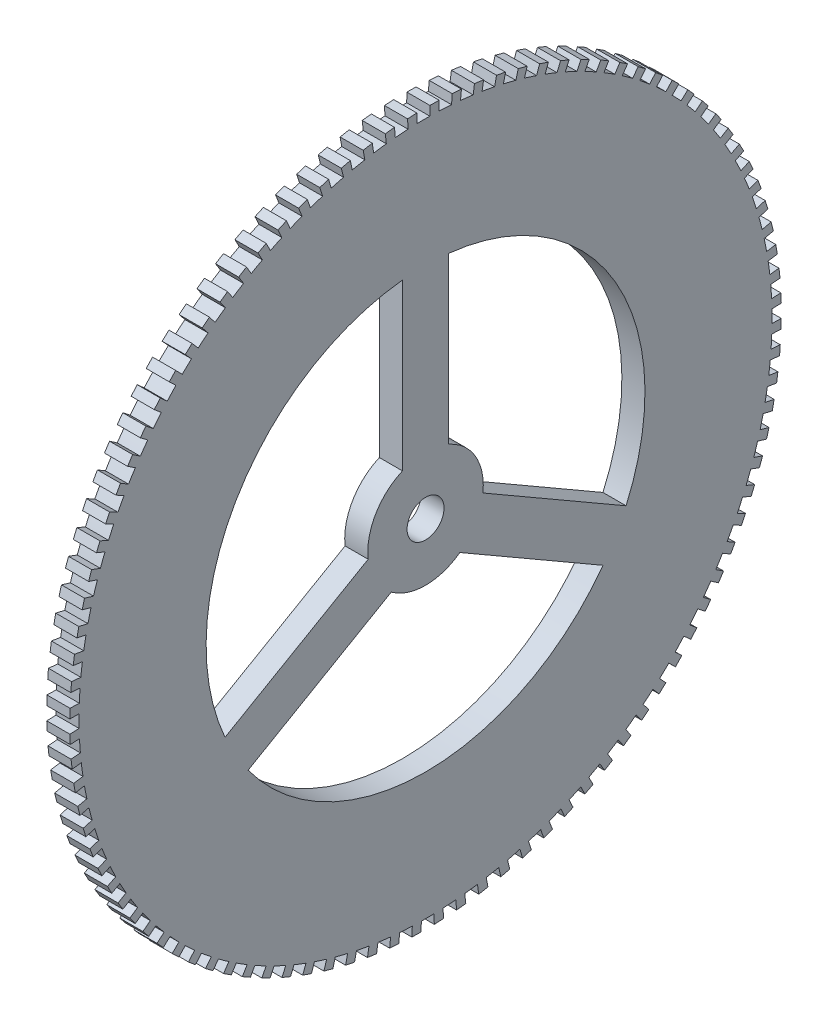
SolidWorks part; units mm, degrees
ref_plane "Front Plane" through (0, 0, 0) normal (0, 0, 1) x (1, 0, 0)
ref_plane "Top Plane" through (0, 0, 0) normal (0, 1, 0) x (1, 0, 0)
ref_plane "Right Plane" through (0, 0, 0) normal (1, 0, 0) x (0, 0, -1)
sketch "Sketch1" plane through (0, 0, 0) normal (1, 0, 0) x (0, 0, -1)
  line L0 (5, 47.2361) -> (5, 11.4564)
  line L1 (-26.7494, 70.0676) -> (-27.4627, 71.9361)
  line L2 (-5, 47.2361) -> (-5, 11.4564)
  line L3 (0, 55) -> (0, -55) construction
  line L4 (43.4077, -19.2879) -> (12.4216, -1.3981)
  line L5 (38.4077, -27.9482) -> (7.4216, -10.0583)
  line L6 (-38.4077, -27.9482) -> (-7.4216, -10.0583)
  line L7 (-43.4077, -19.2879) -> (-12.4216, -1.3981)
  line L8 (-24.9211, 70.7385) -> (-25.5942, 72.6494)
  line L9 (-25.5942, 72.6494) -> (-27.4627, 71.9361)
  line L10 (-22.297, 71.609) -> (-22.8916, 73.5185)
  line L11 (-20.982, 74.1131) -> (-22.8916, 73.5185)
  line L12 (-20.4302, 72.1638) -> (-20.982, 74.1131)
  line L13 (-17.7567, 72.8677) -> (-18.2302, 74.8108)
  line L14 (-16.287, 75.2843) -> (-18.2302, 74.8108)
  line L15 (-15.8587, 73.3042) -> (-16.287, 75.2843)
  line L16 (-13.1462, 73.8389) -> (-13.4968, 75.8079)
  line L17 (-11.5278, 76.1585) -> (-13.4968, 75.8079)
  line L18 (-11.2246, 74.1553) -> (-11.5278, 76.1585)
  line L19 (-8.4839, 74.5186) -> (-8.7102, 76.5058)
  line L20 (-6.723, 76.732) -> (-8.7102, 76.5058)
  line L21 (-6.5462, 74.7138) -> (-6.723, 76.732)
  line L22 (-3.7881, 74.9043) -> (-3.8891, 76.9017)
  line L23 (-1.8917, 77.0027) -> (-3.8891, 76.9017)
  line L24 (-1.8419, 74.9774) -> (-1.8917, 77.0027)
  line L25 (0.9226, 74.9943) -> (0.9472, 76.9942)
  line L26 (2.9471, 76.9696) -> (0.9472, 76.9942)
  line L27 (2.8696, 74.9451) -> (2.9471, 76.9696)
  line L28 (5.6298, 74.7884) -> (5.7799, 76.7828)
  line L29 (7.7742, 76.6326) -> (5.7799, 76.7828)
  line L30 (7.5698, 74.617) -> (7.7742, 76.6326)
  line L31 (10.3146, 74.2873) -> (10.5897, 76.2683)
  line L32 (12.5707, 75.9933) -> (10.5897, 76.2683)
  line L33 (12.2401, 73.9945) -> (12.5707, 75.9933)
  line L34 (14.9588, 73.4931) -> (15.3577, 75.4529)
  line L35 (17.3176, 75.054) -> (15.3577, 75.4529)
  line L36 (16.8621, 73.0799) -> (17.3176, 75.054)
  line L37 (19.544, 72.4088) -> (20.0652, 74.3397)
  line L38 (21.9961, 73.8185) -> (20.0652, 74.3397)
  line L39 (21.4175, 71.8769) -> (21.9961, 73.8185)
  line L40 (24.052, 71.0387) -> (24.6934, 72.9331)
  line L41 (26.5878, 72.2917) -> (24.6934, 72.9331)
  line L42 (25.8884, 70.3903) -> (26.5878, 72.2917)
  line L43 (28.4651, 69.3883) -> (29.2242, 71.2387)
  line L44 (31.0745, 70.4796) -> (29.2242, 71.2387)
  line L45 (30.2572, 68.6258) -> (31.0745, 70.4796)
  line L46 (32.7659, 67.4641) -> (33.6396, 69.2631)
  line L47 (35.4387, 68.3893) -> (33.6396, 69.2631)
  line L48 (34.5065, 66.5905) -> (35.4387, 68.3893)
  line L49 (36.9373, 65.2735) -> (37.9223, 67.0142)
  line L50 (39.6629, 66.0292) -> (37.9223, 67.0142)
  line L51 (38.6197, 64.2924) -> (39.6629, 66.0292)
  line L52 (40.963, 62.8254) -> (42.0553, 64.5008)
  line L53 (43.7307, 63.4084) -> (42.0553, 64.5008)
  line L54 (42.5805, 61.7406) -> (43.7307, 63.4084)
  line L55 (44.827, 60.1294) -> (46.0224, 61.7328)
  line L56 (47.6258, 60.5374) -> (46.0224, 61.7328)
  line L57 (46.3732, 58.9451) -> (47.6258, 60.5374)
  line L58 (48.5141, 57.196) -> (49.8078, 58.7212)
  line L59 (51.333, 57.4275) -> (49.8078, 58.7212)
  line L60 (49.9828, 55.917) -> (51.333, 57.4275)
  line L61 (52.0097, 54.0369) -> (53.3967, 55.4779)
  line L62 (54.8376, 54.091) -> (53.3967, 55.4779)
  line L63 (53.3953, 52.6683) -> (54.8376, 54.091)
  line L64 (55.3001, 50.6646) -> (56.7748, 52.0156)
  line L65 (58.1258, 50.541) -> (56.7748, 52.0156)
  line L66 (56.597, 49.2116) -> (58.1258, 50.541)
  line L67 (58.3722, 47.0923) -> (59.9288, 48.3481)
  line L68 (61.1846, 46.7915) -> (59.9288, 48.3481)
  line L69 (59.5753, 45.5607) -> (61.1846, 46.7915)
  line L70 (61.214, 43.3341) -> (62.8464, 44.4897)
  line L71 (64.0019, 42.8573) -> (62.8464, 44.4897)
  line L72 (62.3185, 41.7301) -> (64.0019, 42.8573)
  line L73 (63.8142, 39.405) -> (65.5159, 40.4558)
  line L74 (66.5667, 38.754) -> (65.5159, 40.4558)
  line L75 (64.8158, 37.7347) -> (66.5667, 38.754)
  line L76 (66.1625, 35.3203) -> (67.9268, 36.2621)
  line L77 (68.8687, 34.4978) -> (67.9268, 36.2621)
  line L78 (67.0573, 33.5904) -> (68.8687, 34.4978)
  line L79 (68.2497, 31.0962) -> (70.0697, 31.9254)
  line L80 (70.899, 30.1054) -> (70.0697, 31.9254)
  line L81 (69.0341, 29.3136) -> (70.899, 30.1054)
  line L82 (70.0676, 26.7494) -> (71.9361, 27.4627)
  line L83 (72.6494, 25.5942) -> (71.9361, 27.4627)
  line L84 (70.7385, 24.9211) -> (72.6494, 25.5942)
  line L85 (71.609, 22.297) -> (73.5185, 22.8916)
  line L86 (74.1131, 20.982) -> (73.5185, 22.8916)
  line L87 (72.1638, 20.4302) -> (74.1131, 20.982)
  line L88 (72.8677, 17.7567) -> (74.8108, 18.2302)
  line L89 (75.2843, 16.287) -> (74.8108, 18.2302)
  line L90 (73.3042, 15.8587) -> (75.2843, 16.287)
  line L91 (73.8389, 13.1462) -> (75.8079, 13.4968)
  line L92 (76.1585, 11.5278) -> (75.8079, 13.4968)
  line L93 (74.1553, 11.2246) -> (76.1585, 11.5278)
  line L94 (74.5186, 8.4839) -> (76.5058, 8.7102)
  line L95 (76.732, 6.723) -> (76.5058, 8.7102)
  line L96 (74.7138, 6.5462) -> (76.732, 6.723)
  line L97 (74.9043, 3.7881) -> (76.9017, 3.8891)
  line L98 (77.0027, 1.8917) -> (76.9017, 3.8891)
  line L99 (74.9774, 1.8419) -> (77.0027, 1.8917)
  line L100 (74.9943, -0.9226) -> (76.9942, -0.9472)
  line L101 (76.9696, -2.9471) -> (76.9942, -0.9472)
  line L102 (74.9451, -2.8696) -> (76.9696, -2.9471)
  line L103 (74.7884, -5.6298) -> (76.7828, -5.7799)
  line L104 (76.6326, -7.7742) -> (76.7828, -5.7799)
  line L105 (74.617, -7.5698) -> (76.6326, -7.7742)
  line L106 (74.2873, -10.3146) -> (76.2683, -10.5897)
  line L107 (75.9933, -12.5707) -> (76.2683, -10.5897)
  line L108 (73.9945, -12.2401) -> (75.9933, -12.5707)
  line L109 (73.4931, -14.9588) -> (75.4529, -15.3577)
  line L110 (75.054, -17.3176) -> (75.4529, -15.3577)
  line L111 (73.0799, -16.8621) -> (75.054, -17.3176)
  line L112 (72.4088, -19.544) -> (74.3397, -20.0652)
  line L113 (73.8185, -21.9961) -> (74.3397, -20.0652)
  line L114 (71.8769, -21.4175) -> (73.8185, -21.9961)
  line L115 (71.0387, -24.052) -> (72.9331, -24.6934)
  line L116 (72.2917, -26.5878) -> (72.9331, -24.6934)
  line L117 (70.3903, -25.8884) -> (72.2917, -26.5878)
  line L118 (69.3883, -28.4651) -> (71.2387, -29.2242)
  line L119 (70.4796, -31.0745) -> (71.2387, -29.2242)
  line L120 (68.6258, -30.2572) -> (70.4796, -31.0745)
  line L121 (67.4641, -32.7659) -> (69.2631, -33.6396)
  line L122 (68.3893, -35.4387) -> (69.2631, -33.6396)
  line L123 (66.5905, -34.5065) -> (68.3893, -35.4387)
  line L124 (65.2735, -36.9373) -> (67.0142, -37.9223)
  line L125 (66.0292, -39.6629) -> (67.0142, -37.9223)
  line L126 (64.2924, -38.6197) -> (66.0292, -39.6629)
  line L127 (62.8254, -40.963) -> (64.5008, -42.0553)
  line L128 (63.4084, -43.7307) -> (64.5008, -42.0553)
  line L129 (61.7406, -42.5805) -> (63.4084, -43.7307)
  line L130 (60.1294, -44.827) -> (61.7328, -46.0224)
  line L131 (60.5374, -47.6258) -> (61.7328, -46.0224)
  line L132 (58.9451, -46.3732) -> (60.5374, -47.6258)
  line L133 (57.196, -48.5141) -> (58.7212, -49.8078)
  line L134 (57.4275, -51.333) -> (58.7212, -49.8078)
  line L135 (55.917, -49.9828) -> (57.4275, -51.333)
  line L136 (54.0369, -52.0097) -> (55.4779, -53.3967)
  line L137 (54.091, -54.8376) -> (55.4779, -53.3967)
  line L138 (52.6683, -53.3953) -> (54.091, -54.8376)
  line L139 (50.6646, -55.3001) -> (52.0156, -56.7748)
  line L140 (50.541, -58.1258) -> (52.0156, -56.7748)
  line L141 (49.2116, -56.597) -> (50.541, -58.1258)
  line L142 (47.0923, -58.3722) -> (48.3481, -59.9288)
  line L143 (46.7915, -61.1846) -> (48.3481, -59.9288)
  line L144 (45.5607, -59.5753) -> (46.7915, -61.1846)
  line L145 (43.3341, -61.214) -> (44.4897, -62.8464)
  line L146 (42.8573, -64.0019) -> (44.4897, -62.8464)
  line L147 (41.7301, -62.3185) -> (42.8573, -64.0019)
  line L148 (39.405, -63.8142) -> (40.4558, -65.5159)
  line L149 (38.754, -66.5667) -> (40.4558, -65.5159)
  line L150 (37.7347, -64.8158) -> (38.754, -66.5667)
  line L151 (35.3203, -66.1625) -> (36.2621, -67.9268)
  line L152 (34.4978, -68.8687) -> (36.2621, -67.9268)
  line L153 (33.5904, -67.0573) -> (34.4978, -68.8687)
  line L154 (31.0962, -68.2497) -> (31.9254, -70.0697)
  line L155 (30.1054, -70.899) -> (31.9254, -70.0697)
  line L156 (29.3136, -69.0341) -> (30.1054, -70.899)
  line L157 (26.7494, -70.0676) -> (27.4627, -71.9361)
  line L158 (25.5942, -72.6494) -> (27.4627, -71.9361)
  line L159 (24.9211, -70.7385) -> (25.5942, -72.6494)
  line L160 (22.297, -71.609) -> (22.8916, -73.5185)
  line L161 (20.982, -74.1131) -> (22.8916, -73.5185)
  line L162 (20.4302, -72.1638) -> (20.982, -74.1131)
  line L163 (17.7567, -72.8677) -> (18.2302, -74.8108)
  line L164 (16.287, -75.2843) -> (18.2302, -74.8108)
  line L165 (15.8587, -73.3042) -> (16.287, -75.2843)
  line L166 (13.1462, -73.8389) -> (13.4968, -75.8079)
  line L167 (11.5278, -76.1585) -> (13.4968, -75.8079)
  line L168 (11.2246, -74.1553) -> (11.5278, -76.1585)
  line L169 (8.4839, -74.5186) -> (8.7102, -76.5058)
  line L170 (6.723, -76.732) -> (8.7102, -76.5058)
  line L171 (6.5462, -74.7138) -> (6.723, -76.732)
  line L172 (3.7881, -74.9043) -> (3.8891, -76.9017)
  line L173 (1.8917, -77.0027) -> (3.8891, -76.9017)
  line L174 (1.8419, -74.9774) -> (1.8917, -77.0027)
  line L175 (-0.9226, -74.9943) -> (-0.9472, -76.9942)
  line L176 (-2.9471, -76.9696) -> (-0.9472, -76.9942)
  line L177 (-2.8696, -74.9451) -> (-2.9471, -76.9696)
  line L178 (-5.6298, -74.7884) -> (-5.7799, -76.7828)
  line L179 (-7.7742, -76.6326) -> (-5.7799, -76.7828)
  line L180 (-7.5698, -74.617) -> (-7.7742, -76.6326)
  line L181 (-10.3146, -74.2873) -> (-10.5897, -76.2683)
  line L182 (-12.5707, -75.9933) -> (-10.5897, -76.2683)
  line L183 (-12.2401, -73.9945) -> (-12.5707, -75.9933)
  line L184 (-14.9588, -73.4931) -> (-15.3577, -75.4529)
  line L185 (-17.3176, -75.054) -> (-15.3577, -75.4529)
  line L186 (-16.8621, -73.0799) -> (-17.3176, -75.054)
  line L187 (-19.544, -72.4088) -> (-20.0652, -74.3397)
  line L188 (-21.9961, -73.8185) -> (-20.0652, -74.3397)
  line L189 (-21.4175, -71.8769) -> (-21.9961, -73.8185)
  line L190 (-24.052, -71.0387) -> (-24.6934, -72.9331)
  line L191 (-26.5878, -72.2917) -> (-24.6934, -72.9331)
  line L192 (-25.8884, -70.3903) -> (-26.5878, -72.2917)
  line L193 (-28.4651, -69.3883) -> (-29.2242, -71.2387)
  line L194 (-31.0745, -70.4796) -> (-29.2242, -71.2387)
  line L195 (-30.2572, -68.6258) -> (-31.0745, -70.4796)
  line L196 (-32.7659, -67.4641) -> (-33.6396, -69.2631)
  line L197 (-35.4387, -68.3893) -> (-33.6396, -69.2631)
  line L198 (-34.5065, -66.5905) -> (-35.4387, -68.3893)
  line L199 (-36.9373, -65.2735) -> (-37.9223, -67.0142)
  line L200 (-39.6629, -66.0292) -> (-37.9223, -67.0142)
  line L201 (-38.6197, -64.2924) -> (-39.6629, -66.0292)
  line L202 (-40.963, -62.8254) -> (-42.0553, -64.5008)
  line L203 (-43.7307, -63.4084) -> (-42.0553, -64.5008)
  line L204 (-42.5805, -61.7406) -> (-43.7307, -63.4084)
  line L205 (-44.827, -60.1294) -> (-46.0224, -61.7328)
  line L206 (-47.6258, -60.5374) -> (-46.0224, -61.7328)
  line L207 (-46.3732, -58.9451) -> (-47.6258, -60.5374)
  line L208 (-48.5141, -57.196) -> (-49.8078, -58.7212)
  line L209 (-51.333, -57.4275) -> (-49.8078, -58.7212)
  line L210 (-49.9828, -55.917) -> (-51.333, -57.4275)
  line L211 (-52.0097, -54.0369) -> (-53.3967, -55.4779)
  line L212 (-54.8376, -54.091) -> (-53.3967, -55.4779)
  line L213 (-53.3953, -52.6683) -> (-54.8376, -54.091)
  line L214 (-55.3001, -50.6646) -> (-56.7748, -52.0156)
  line L215 (-58.1258, -50.541) -> (-56.7748, -52.0156)
  line L216 (-56.597, -49.2116) -> (-58.1258, -50.541)
  line L217 (-58.3722, -47.0923) -> (-59.9288, -48.3481)
  line L218 (-61.1846, -46.7915) -> (-59.9288, -48.3481)
  line L219 (-59.5753, -45.5607) -> (-61.1846, -46.7915)
  line L220 (-61.214, -43.3341) -> (-62.8464, -44.4897)
  line L221 (-64.0019, -42.8573) -> (-62.8464, -44.4897)
  line L222 (-62.3185, -41.7301) -> (-64.0019, -42.8573)
  line L223 (-63.8142, -39.405) -> (-65.5159, -40.4558)
  line L224 (-66.5667, -38.754) -> (-65.5159, -40.4558)
  line L225 (-64.8158, -37.7347) -> (-66.5667, -38.754)
  line L226 (-66.1625, -35.3203) -> (-67.9268, -36.2621)
  line L227 (-68.8687, -34.4978) -> (-67.9268, -36.2621)
  line L228 (-67.0573, -33.5904) -> (-68.8687, -34.4978)
  line L229 (-68.2497, -31.0962) -> (-70.0697, -31.9254)
  line L230 (-70.899, -30.1054) -> (-70.0697, -31.9254)
  line L231 (-69.0341, -29.3136) -> (-70.899, -30.1054)
  line L232 (-70.0676, -26.7494) -> (-71.9361, -27.4627)
  line L233 (-72.6494, -25.5942) -> (-71.9361, -27.4627)
  line L234 (-70.7385, -24.9211) -> (-72.6494, -25.5942)
  line L235 (-71.609, -22.297) -> (-73.5185, -22.8916)
  line L236 (-74.1131, -20.982) -> (-73.5185, -22.8916)
  line L237 (-72.1638, -20.4302) -> (-74.1131, -20.982)
  line L238 (-72.8677, -17.7567) -> (-74.8108, -18.2302)
  line L239 (-75.2843, -16.287) -> (-74.8108, -18.2302)
  line L240 (-73.3042, -15.8587) -> (-75.2843, -16.287)
  line L241 (-73.8389, -13.1462) -> (-75.8079, -13.4968)
  line L242 (-76.1585, -11.5278) -> (-75.8079, -13.4968)
  line L243 (-74.1553, -11.2246) -> (-76.1585, -11.5278)
  line L244 (-74.5186, -8.4839) -> (-76.5058, -8.7102)
  line L245 (-76.732, -6.723) -> (-76.5058, -8.7102)
  line L246 (-74.7138, -6.5462) -> (-76.732, -6.723)
  line L247 (-74.9043, -3.7881) -> (-76.9017, -3.8891)
  line L248 (-77.0027, -1.8917) -> (-76.9017, -3.8891)
  line L249 (-74.9774, -1.8419) -> (-77.0027, -1.8917)
  line L250 (-74.9943, 0.9226) -> (-76.9942, 0.9472)
  line L251 (-76.9696, 2.9471) -> (-76.9942, 0.9472)
  line L252 (-74.9451, 2.8696) -> (-76.9696, 2.9471)
  line L253 (-74.7884, 5.6298) -> (-76.7828, 5.7799)
  line L254 (-76.6326, 7.7742) -> (-76.7828, 5.7799)
  line L255 (-74.617, 7.5698) -> (-76.6326, 7.7742)
  line L256 (-74.2873, 10.3146) -> (-76.2683, 10.5897)
  line L257 (-75.9933, 12.5707) -> (-76.2683, 10.5897)
  line L258 (-73.9945, 12.2401) -> (-75.9933, 12.5707)
  line L259 (-73.4931, 14.9588) -> (-75.4529, 15.3577)
  line L260 (-75.054, 17.3176) -> (-75.4529, 15.3577)
  line L261 (-73.0799, 16.8621) -> (-75.054, 17.3176)
  line L262 (-72.4088, 19.544) -> (-74.3397, 20.0652)
  line L263 (-73.8185, 21.9961) -> (-74.3397, 20.0652)
  line L264 (-71.8769, 21.4175) -> (-73.8185, 21.9961)
  line L265 (-71.0387, 24.052) -> (-72.9331, 24.6934)
  line L266 (-72.2917, 26.5878) -> (-72.9331, 24.6934)
  line L267 (-70.3903, 25.8884) -> (-72.2917, 26.5878)
  line L268 (-69.3883, 28.4651) -> (-71.2387, 29.2242)
  line L269 (-70.4796, 31.0745) -> (-71.2387, 29.2242)
  line L270 (-68.6258, 30.2572) -> (-70.4796, 31.0745)
  line L271 (-67.4641, 32.7659) -> (-69.2631, 33.6396)
  line L272 (-68.3893, 35.4387) -> (-69.2631, 33.6396)
  line L273 (-66.5905, 34.5065) -> (-68.3893, 35.4387)
  line L274 (-65.2735, 36.9373) -> (-67.0142, 37.9223)
  line L275 (-66.0292, 39.6629) -> (-67.0142, 37.9223)
  line L276 (-64.2924, 38.6197) -> (-66.0292, 39.6629)
  line L277 (-62.8254, 40.963) -> (-64.5008, 42.0553)
  line L278 (-63.4084, 43.7307) -> (-64.5008, 42.0553)
  line L279 (-61.7406, 42.5805) -> (-63.4084, 43.7307)
  line L280 (-60.1294, 44.827) -> (-61.7328, 46.0224)
  line L281 (-60.5374, 47.6258) -> (-61.7328, 46.0224)
  line L282 (-58.9451, 46.3732) -> (-60.5374, 47.6258)
  line L283 (-57.196, 48.5141) -> (-58.7212, 49.8078)
  line L284 (-57.4275, 51.333) -> (-58.7212, 49.8078)
  line L285 (-55.917, 49.9828) -> (-57.4275, 51.333)
  line L286 (-54.0369, 52.0097) -> (-55.4779, 53.3967)
  line L287 (-54.091, 54.8376) -> (-55.4779, 53.3967)
  line L288 (-52.6683, 53.3953) -> (-54.091, 54.8376)
  line L289 (-50.6646, 55.3001) -> (-52.0156, 56.7748)
  line L290 (-50.541, 58.1258) -> (-52.0156, 56.7748)
  line L291 (-49.2116, 56.597) -> (-50.541, 58.1258)
  line L292 (-47.0923, 58.3722) -> (-48.3481, 59.9288)
  line L293 (-46.7915, 61.1846) -> (-48.3481, 59.9288)
  line L294 (-45.5607, 59.5753) -> (-46.7915, 61.1846)
  line L295 (-43.3341, 61.214) -> (-44.4897, 62.8464)
  line L296 (-42.8573, 64.0019) -> (-44.4897, 62.8464)
  line L297 (-41.7301, 62.3185) -> (-42.8573, 64.0019)
  line L298 (-39.405, 63.8142) -> (-40.4558, 65.5159)
  line L299 (-38.754, 66.5667) -> (-40.4558, 65.5159)
  line L300 (-37.7347, 64.8158) -> (-38.754, 66.5667)
  line L301 (-35.3203, 66.1625) -> (-36.2621, 67.9268)
  line L302 (-34.4978, 68.8687) -> (-36.2621, 67.9268)
  line L303 (-33.5904, 67.0573) -> (-34.4978, 68.8687)
  line L304 (-31.0962, 68.2497) -> (-31.9254, 70.0697)
  line L305 (-30.1054, 70.899) -> (-31.9254, 70.0697)
  line L306 (-29.3136, 69.0341) -> (-30.1054, 70.899)
  arc A0 (-5, 47.2361) -> (-43.4077, -19.2879) centre (0, 0) ccw
  arc A1 (-26.7494, 70.0676) -> (-29.3136, 69.0341) centre (0, 0) ccw
  arc A2 (-5, 11.4564) -> (-12.4216, -1.3981) centre (0, 0) ccw
  arc A3 (-38.4077, -27.9482) -> (38.4077, -27.9482) centre (0, 0) ccw
  arc A4 (43.4077, -19.2879) -> (5, 47.2361) centre (0, 0) ccw
  arc A5 (12.4216, -1.3981) -> (5, 11.4564) centre (0, 0) ccw
  arc A6 (-7.4216, -10.0583) -> (7.4216, -10.0583) centre (0, 0) ccw
  circle A7 centre (0, 0) radius 4
  arc A8 (-22.297, 71.609) -> (-24.9211, 70.7385) centre (0, 0) ccw
  arc A9 (-17.7567, 72.8677) -> (-20.4302, 72.1638) centre (0, 0) ccw
  arc A10 (-13.1462, 73.8389) -> (-15.8587, 73.3042) centre (0, 0) ccw
  arc A11 (-8.4839, 74.5186) -> (-11.2246, 74.1553) centre (0, 0) ccw
  arc A12 (-3.7881, 74.9043) -> (-6.5462, 74.7138) centre (0, 0) ccw
  arc A13 (0.9226, 74.9943) -> (-1.8419, 74.9774) centre (0, 0) ccw
  arc A14 (5.6298, 74.7884) -> (2.8696, 74.9451) centre (0, 0) ccw
  arc A15 (10.3146, 74.2873) -> (7.5698, 74.617) centre (0, 0) ccw
  arc A16 (14.9588, 73.4931) -> (12.2401, 73.9945) centre (0, 0) ccw
  arc A17 (19.544, 72.4088) -> (16.8621, 73.0799) centre (0, 0) ccw
  arc A18 (24.052, 71.0387) -> (21.4175, 71.8769) centre (0, 0) ccw
  arc A19 (28.4651, 69.3883) -> (25.8884, 70.3903) centre (0, 0) ccw
  arc A20 (32.7659, 67.4641) -> (30.2572, 68.6258) centre (0, 0) ccw
  arc A21 (36.9373, 65.2735) -> (34.5065, 66.5905) centre (0, 0) ccw
  arc A22 (40.963, 62.8254) -> (38.6197, 64.2924) centre (0, 0) ccw
  arc A23 (44.827, 60.1294) -> (42.5805, 61.7406) centre (0, 0) ccw
  arc A24 (48.5141, 57.196) -> (46.3732, 58.9451) centre (0, 0) ccw
  arc A25 (52.0097, 54.0369) -> (49.9828, 55.917) centre (0, 0) ccw
  arc A26 (55.3001, 50.6646) -> (53.3953, 52.6683) centre (0, 0) ccw
  arc A27 (58.3722, 47.0923) -> (56.597, 49.2116) centre (0, 0) ccw
  arc A28 (61.214, 43.3341) -> (59.5753, 45.5607) centre (0, 0) ccw
  arc A29 (63.8142, 39.405) -> (62.3185, 41.7301) centre (0, 0) ccw
  arc A30 (66.1625, 35.3203) -> (64.8158, 37.7347) centre (0, 0) ccw
  arc A31 (68.2497, 31.0962) -> (67.0573, 33.5904) centre (0, 0) ccw
  arc A32 (70.0676, 26.7494) -> (69.0341, 29.3136) centre (0, 0) ccw
  arc A33 (71.609, 22.297) -> (70.7385, 24.9211) centre (0, 0) ccw
  arc A34 (72.8677, 17.7567) -> (72.1638, 20.4302) centre (0, 0) ccw
  arc A35 (73.8389, 13.1462) -> (73.3042, 15.8587) centre (0, 0) ccw
  arc A36 (74.5186, 8.4839) -> (74.1553, 11.2246) centre (0, 0) ccw
  arc A37 (74.9043, 3.7881) -> (74.7138, 6.5462) centre (0, 0) ccw
  arc A38 (74.9943, -0.9226) -> (74.9774, 1.8419) centre (0, 0) ccw
  arc A39 (74.7884, -5.6298) -> (74.9451, -2.8696) centre (0, 0) ccw
  arc A40 (74.2873, -10.3146) -> (74.617, -7.5698) centre (0, 0) ccw
  arc A41 (73.4931, -14.9588) -> (73.9945, -12.2401) centre (0, 0) ccw
  arc A42 (72.4088, -19.544) -> (73.0799, -16.8621) centre (0, 0) ccw
  arc A43 (71.0387, -24.052) -> (71.8769, -21.4175) centre (0, 0) ccw
  arc A44 (69.3883, -28.4651) -> (70.3903, -25.8884) centre (0, 0) ccw
  arc A45 (67.4641, -32.7659) -> (68.6258, -30.2572) centre (0, 0) ccw
  arc A46 (65.2735, -36.9373) -> (66.5905, -34.5065) centre (0, 0) ccw
  arc A47 (62.8254, -40.963) -> (64.2924, -38.6197) centre (0, 0) ccw
  arc A48 (60.1294, -44.827) -> (61.7406, -42.5805) centre (0, 0) ccw
  arc A49 (57.196, -48.5141) -> (58.9451, -46.3732) centre (0, 0) ccw
  arc A50 (54.0369, -52.0097) -> (55.917, -49.9828) centre (0, 0) ccw
  arc A51 (50.6646, -55.3001) -> (52.6683, -53.3953) centre (0, 0) ccw
  arc A52 (47.0923, -58.3722) -> (49.2116, -56.597) centre (0, 0) ccw
  arc A53 (43.3341, -61.214) -> (45.5607, -59.5753) centre (0, 0) ccw
  arc A54 (39.405, -63.8142) -> (41.7301, -62.3185) centre (0, 0) ccw
  arc A55 (35.3203, -66.1625) -> (37.7347, -64.8158) centre (0, 0) ccw
  arc A56 (31.0962, -68.2497) -> (33.5904, -67.0573) centre (0, 0) ccw
  arc A57 (26.7494, -70.0676) -> (29.3136, -69.0341) centre (0, 0) ccw
  arc A58 (22.297, -71.609) -> (24.9211, -70.7385) centre (0, 0) ccw
  arc A59 (17.7567, -72.8677) -> (20.4302, -72.1638) centre (0, 0) ccw
  arc A60 (13.1462, -73.8389) -> (15.8587, -73.3042) centre (0, 0) ccw
  arc A61 (8.4839, -74.5186) -> (11.2246, -74.1553) centre (0, 0) ccw
  arc A62 (-5.6298, -74.7884) -> (-2.8696, -74.9451) centre (0, 0) ccw
  arc A63 (-10.3146, -74.2873) -> (-7.5698, -74.617) centre (0, 0) ccw
  arc A64 (-14.9588, -73.4931) -> (-12.2401, -73.9945) centre (0, 0) ccw
  arc A65 (-19.544, -72.4088) -> (-16.8621, -73.0799) centre (0, 0) ccw
  arc A66 (-24.052, -71.0387) -> (-21.4175, -71.8769) centre (0, 0) ccw
  arc A67 (-28.4651, -69.3883) -> (-25.8884, -70.3903) centre (0, 0) ccw
  arc A68 (-32.7659, -67.4641) -> (-30.2572, -68.6258) centre (0, 0) ccw
  arc A69 (-36.9373, -65.2735) -> (-34.5065, -66.5905) centre (0, 0) ccw
  arc A70 (-40.963, -62.8254) -> (-38.6197, -64.2924) centre (0, 0) ccw
  arc A71 (-44.827, -60.1294) -> (-42.5805, -61.7406) centre (0, 0) ccw
  arc A72 (-48.5141, -57.196) -> (-46.3732, -58.9451) centre (0, 0) ccw
  arc A73 (-52.0097, -54.0369) -> (-49.9828, -55.917) centre (0, 0) ccw
  arc A74 (-55.3001, -50.6646) -> (-53.3953, -52.6683) centre (0, 0) ccw
  arc A75 (-58.3722, -47.0923) -> (-56.597, -49.2116) centre (0, 0) ccw
  arc A76 (-61.214, -43.3341) -> (-59.5753, -45.5607) centre (0, 0) ccw
  arc A77 (-63.8142, -39.405) -> (-62.3185, -41.7301) centre (0, 0) ccw
  arc A78 (-66.1625, -35.3203) -> (-64.8158, -37.7347) centre (0, 0) ccw
  arc A79 (-68.2497, -31.0962) -> (-67.0573, -33.5904) centre (0, 0) ccw
  arc A80 (-70.0676, -26.7494) -> (-69.0341, -29.3136) centre (0, 0) ccw
  arc A81 (-71.609, -22.297) -> (-70.7385, -24.9211) centre (0, 0) ccw
  arc A82 (-72.8677, -17.7567) -> (-72.1638, -20.4302) centre (0, 0) ccw
  arc A83 (-73.8389, -13.1462) -> (-73.3042, -15.8587) centre (0, 0) ccw
  arc A84 (-74.5186, -8.4839) -> (-74.1553, -11.2246) centre (0, 0) ccw
  arc A85 (-74.9043, -3.7881) -> (-74.7138, -6.5462) centre (0, 0) ccw
  arc A86 (-74.9943, 0.9226) -> (-74.9774, -1.8419) centre (0, 0) ccw
  arc A87 (-74.7884, 5.6298) -> (-74.9451, 2.8696) centre (0, 0) ccw
  arc A88 (-74.2873, 10.3146) -> (-74.617, 7.5698) centre (0, 0) ccw
  arc A89 (-73.4931, 14.9588) -> (-73.9945, 12.2401) centre (0, 0) ccw
  arc A90 (-72.4088, 19.544) -> (-73.0799, 16.8621) centre (0, 0) ccw
  arc A91 (-71.0387, 24.052) -> (-71.8769, 21.4175) centre (0, 0) ccw
  arc A92 (-69.3883, 28.4651) -> (-70.3903, 25.8884) centre (0, 0) ccw
  arc A93 (-67.4641, 32.7659) -> (-68.6258, 30.2572) centre (0, 0) ccw
  arc A94 (-65.2735, 36.9373) -> (-66.5905, 34.5065) centre (0, 0) ccw
  arc A95 (-62.8254, 40.963) -> (-64.2924, 38.6197) centre (0, 0) ccw
  arc A96 (-60.1294, 44.827) -> (-61.7406, 42.5805) centre (0, 0) ccw
  arc A97 (-57.196, 48.5141) -> (-58.9451, 46.3732) centre (0, 0) ccw
  arc A98 (-54.0369, 52.0097) -> (-55.917, 49.9828) centre (0, 0) ccw
  arc A99 (-50.6646, 55.3001) -> (-52.6683, 53.3953) centre (0, 0) ccw
  arc A100 (-47.0923, 58.3722) -> (-49.2116, 56.597) centre (0, 0) ccw
  arc A101 (-43.3341, 61.214) -> (-45.5607, 59.5753) centre (0, 0) ccw
  arc A102 (-39.405, 63.8142) -> (-41.7301, 62.3185) centre (0, 0) ccw
  arc A103 (-35.3203, 66.1625) -> (-37.7347, 64.8158) centre (0, 0) ccw
  arc A104 (-31.0962, 68.2497) -> (-33.5904, 67.0573) centre (0, 0) ccw
  arc A105 (-0.9226, -74.9943) -> (1.8419, -74.9774) centre (0, 0) ccw
  arc A106 (3.7881, -74.9043) -> (6.5462, -74.7138) centre (0, 0) ccw
  point P23 (0, 0)
  point P420 (0, 0)
  dimension "D1" = 95
  dimension "D2" = 150
  dimension "D6" = 25
  dimension "D7" = 8
  dimension "D3" = 5
  dimension "D4" = 10
  dimension "D8" = 2
  dimension "D9" = 2
  dimension "D5" = 3
  dimension "D10" = 100
extrude "Boss-Extrude1" add sketch "Sketch1" along normal blind 5
ref_axis "Axis1" through (-0.25, 0, 0) along (1, 0, 0)
